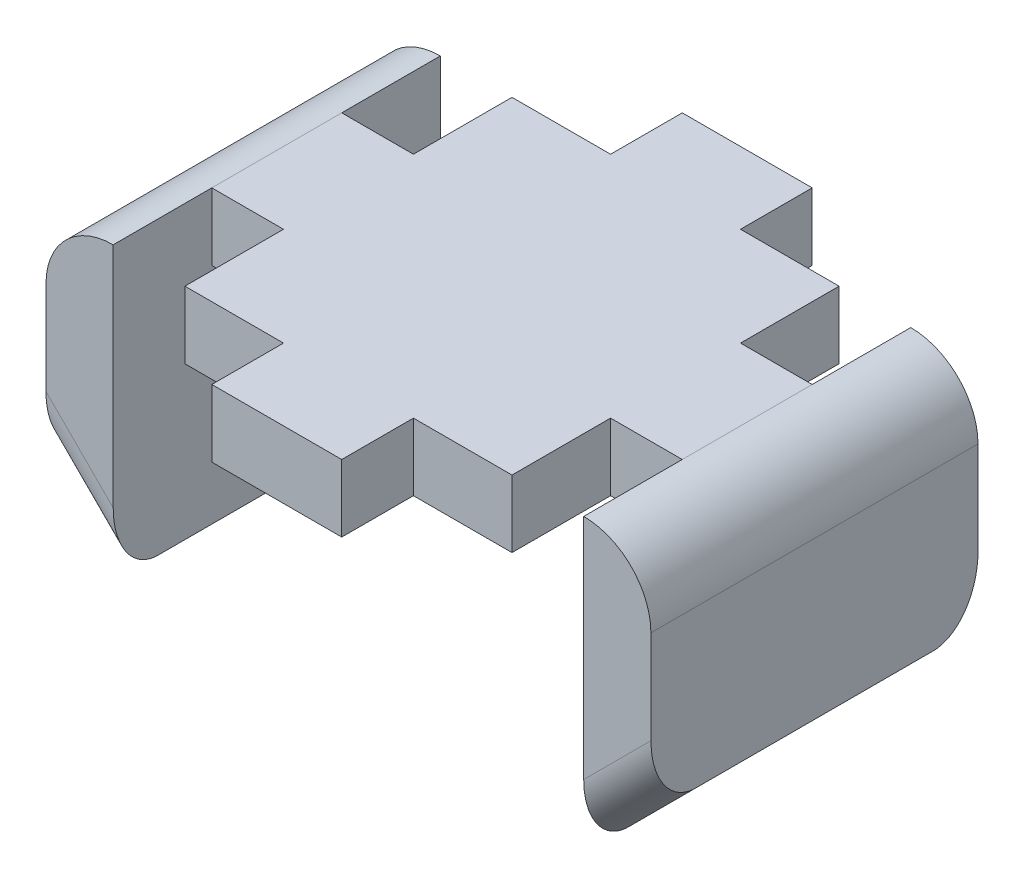
SolidWorks part; units mm, degrees
material "ABS"
ref_plane "Front Plane" through (0, 0, 0) normal (0, 0, 1) x (1, 0, 0)
ref_plane "Top Plane" through (0, 0, 0) normal (0, 1, 0) x (1, 0, 0)
ref_plane "Right Plane" through (0, 0, 0) normal (1, 0, 0) x (0, 0, -1)
sketch "Sketch1" plane through (0, 0, 0) normal (0, 1, 0) x (1, 0, 0)
  line L0 (-7.3, 7.3) -> (7.3, 7.3)
  line L1 (-7.5, 7.5) -> (7.5, 7.5) construction
  line L2 (-7.5, 7.5) -> (-7.5, -7.5) construction
  line L3 (-7.5, -7.5) -> (7.5, -7.5) construction
  line L4 (7.5, 7.5) -> (7.5, -7.5) construction
  line L5 (7.3, 7.3) -> (7.3, -7.3)
  line L6 (-7.3, -7.3) -> (7.3, -7.3)
  line L7 (-7.3, 7.3) -> (-7.3, -7.3)
  point P4 (0, 7.5)
  point P6 (-7.5, 0)
  dimension "D1" = 15
  dimension "D2" = 15
  dimension "D3" = 0.2
extrude "Boss-Extrude1" add sketch "Sketch1" along normal mid plane 3
sketch "Sketch2" plane through (0, 0, 0) normal (0, 1, 0) x (1, 0, 0)
  line L0 (-2.9, 7.3) -> (-2.9, 10.5)
  line L1 (-3, 10.3) -> (3, 10.3) construction
  line L2 (-3, 10.3) -> (-3, 7.3) construction
  line L4 (3, 10.3) -> (3, 7.3) construction
  line L5 (7.3, 7.3) -> (-7.3, 7.3) construction
  line L10 (-2.9, 10.5) -> (2.9, 10.5)
  line L15 (2.9, 10.5) -> (2.9, 7.3)
  line L20 (-2.9, 7.3) -> (2.9, 7.3)
  line L26 (-7.15, 0) -> (7.15, 0) construction
  line L27 (-2.9, -7.3) -> (-2.9, -10.5)
  line L28 (-2.9, -10.5) -> (2.9, -10.5)
  line L29 (2.9, -10.5) -> (2.9, -7.3)
  line L30 (-2.9, -7.3) -> (2.9, -7.3)
  line L31 (-7.3, 2.9) -> (-10.5, 2.9)
  line L32 (-7.3, 7.3) -> (-7.3, -7.3) construction
  line L33 (-10.5, 2.9) -> (-10.5, -2.9)
  line L34 (-10.5, -2.9) -> (-7.3, -2.9)
  line L35 (-7.3, -2.9) -> (-7.3, 2.9)
  line L36 (0, -7.15) -> (0, 7.15) construction
  line L37 (7.3, -2.9) -> (7.3, 2.9)
  line L38 (10.5, -2.9) -> (7.3, -2.9)
  line L39 (10.5, 2.9) -> (10.5, -2.9)
  line L40 (7.3, 2.9) -> (10.5, 2.9)
  point P6 (0, 10.3)
  point P12 (0, 10.5)
  point P22 (-10.5, 0)
  dimension "D1" = 6
  dimension "D2" = 3
  dimension "D3" = 0.2
  dimension "D4" = 0.2
extrude "Boss-Extrude2" add sketch "Sketch2" along normal mid plane 3
sketch "Sketch4" plane through (-10.5, 0, 0) normal (-1, 0, 0) x (0, 0, 1)
  line L0 (7.3, 1.5) -> (7.3, -1.5) construction
  line L6 (-7.3, -1.5) -> (-2.9, -1.5) construction
  line L8 (-7.3, 1.5) -> (7.3, 1.5)
  line L9 (-7.3, 1.5) -> (-7.3, -11.5)
  line L10 (-7.3, -11.5) -> (7.3, -11.5)
  line L11 (7.3, 1.5) -> (7.3, -11.5)
  dimension "D1" = 10
extrude "Boss-Extrude3" add sketch "Sketch4" along normal blind 3
mirror "Mirror1" about plane through (0, 0, 0) normal (1, 0, 0) of "Boss-Extrude3"
fillet "Fillet5" radius 3 2 edges at (-13.5, 1.5, 0) (13.5, 1.5, 0)
chamfer "Chamfer1" distance 3 angle 45 2 edges at (13.5, -11.5, 0) (-13.5, -11.5, 0)
fillet "Fillet4" radius 2 4 edges at (12, -10, 7.3) (12, -10, -7.3) (-12, -10, 7.3) (-12, -10, -7.3)
